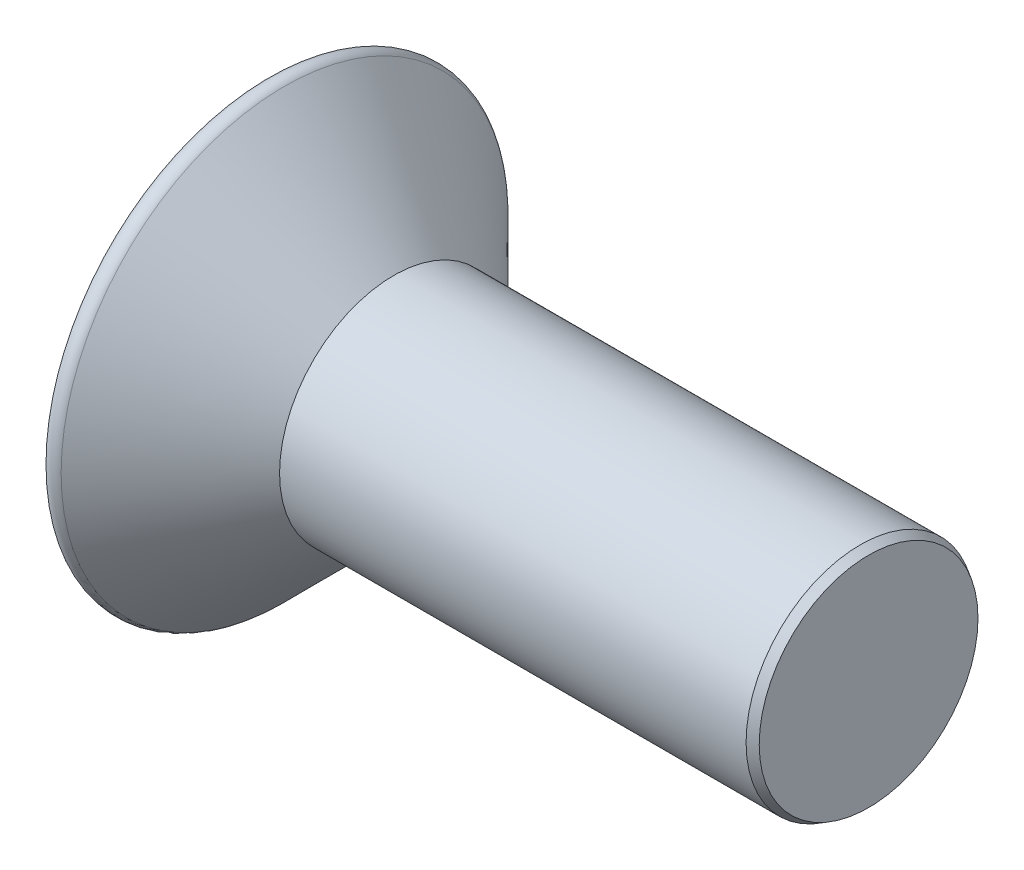
SolidWorks part; units mm, degrees
ref_plane "Front Plane" through (0, 0, 0) normal (0, 0, 1) x (1, 0, 0)
ref_plane "Top Plane" through (0, 0, 0) normal (0, 1, 0) x (1, 0, 0)
ref_plane "Right Plane" through (0, 0, 0) normal (1, 0, 0) x (0, 0, -1)
sketch "Sketch1" plane through (0, 0, 0) normal (0, 0, 1) x (1, 0, 0)
  line L0 (0, 0) -> (6.2784, 0) construction
  line L3 (-7.55, 0) -> (-7.55, -1.8061) construction
  line L4 (-7.55, 0) -> (19.75, 0)
  line L5 (0, 4.75) -> (19.75, 4.75)
  line L6 (19.75, 4.75) -> (19.75, 0)
  line L7 (0, 4.75) -> (-4.5425, 9.2925)
  arc A0 (-5.25, 9.1875) -> (-7.55, 0) centre (11.95, 0) ccw
  arc A1 (-5.25, 9.1875) -> (-4.5425, 9.2925) centre (-4.8573, 8.9777) cw
  dimension "D1" = 45
revolve "Revolve1" add sketch "Sketch1" angle 360 about L0
cosmetic thread "ThreadCosmetic" [suppressed] parameters "D1"=31.8, "D2"=7.85
chamfer "Chamfer1" distance 0.2 angle 60 1 edges at (19.75, 0, 4.75) first distance on face at (19.75, 0, 4.75)
sketch "Sketch5" plane through (0, 0, 0) normal (0, 0, 1) x (1, 0, 0)
  line L0 (1.8337, 3.925) -> (0.6863, 3.925)
  line L1 (0.6863, 3.925) -> (0.21, 4.75)
  line L2 (1.8337, 3.925) -> (2.31, 4.75)
  line L3 (0.21, 4.75) -> (0.21, 5)
  line L4 (2.31, 4.75) -> (2.31, 5)
  line L5 (0.21, 5) -> (2.31, 5)
  line L6 (1.26, 3.925) -> (1.26, 0) construction
  line L7 (0, 0) -> (7.3035, 0) construction
  line L9 (0, 4.75) -> (0, -4.75) construction
  line L12 (19.4036, 4.75) -> (0, 4.75) construction
  dimension "D2" = 60
  dimension "D3" = 0.25
  dimension "minordia" = 7.85
  dimension "threadstart" = 1.26
revolve "ThreadSchematic" [suppressed] cut sketch "Sketch5" angle 360 about L7
pattern_linear "ThdSchPat" [suppressed] count 13 spacing 2.1 along (1, 0, 0) of bodies 105
sketch "Sketch2" plane through (0, 0, 0) normal (0, 0, 1) x (1, 0, 0)
  line L0 (0, 0) -> (5.7679, 0) construction
  line L1 (19.75, 0) -> (11.5228, 4.75)
  line L2 (19.75, 4.75) -> (19.75, 0) construction
  line L4 (11.5228, 4.75) -> (11.5228, 4.85)
  line L5 (11.5228, 4.85) -> (19.85, 4.85)
  line L6 (19.85, 4.85) -> (19.85, 0)
  line L7 (19.85, 0) -> (19.75, 0)
  point P5 (0, 4.75)
  dimension "D1" = 30
  dimension "D2" = 0.1
  dimension "D3" = 0.1
revolve "EndCone" [suppressed] cut sketch "Sketch2" angle 360 about L0
ref_plane "Plane4" through (-7.55, 0, 0) normal (1, 0, 0) x (0, 0, -1)
sketch "Sketch3" plane through (-7.55, 0, 0) normal (1, 0, 0) x (0, 0, -1)
  line L0 (0, 2.343) -> (0, -2.4842) construction
  line L1 (2.7661, 0) -> (-3.4558, 0) construction
  line L2 (-1.04, 5.2) -> (1.04, 5.2)
  line L3 (1.04, 5.2) -> (0.6933, 3.4667)
  line L4 (0, 0) -> (1.9578, 1.9578) construction
  line L5 (0.6933, 3.4667) -> (1.7084, 1.7084)
  line L6 (0.6933, 3.4667) -> (0, 0) construction
  line L7 (-0.6933, 3.4667) -> (-1.7084, 1.7084)
  line L8 (-1.04, 5.2) -> (-0.6933, 3.4667)
  line L9 (5.2, 1.04) -> (5.2, -1.04)
  line L10 (5.2, -1.04) -> (3.4667, -0.6933)
  line L11 (3.4667, -0.6933) -> (1.7084, -1.7084)
  line L12 (3.4667, 0.6933) -> (1.7084, 1.7084)
  line L13 (5.2, 1.04) -> (3.4667, 0.6933)
  line L14 (1.04, -5.2) -> (-1.04, -5.2)
  line L15 (-1.04, -5.2) -> (-0.6933, -3.4667)
  line L16 (-0.6933, -3.4667) -> (-1.7084, -1.7084)
  line L17 (0.6933, -3.4667) -> (1.7084, -1.7084)
  line L18 (1.04, -5.2) -> (0.6933, -3.4667)
  line L19 (-5.2, -1.04) -> (-5.2, 1.04)
  line L20 (-5.2, 1.04) -> (-3.4667, 0.6933)
  line L21 (-3.4667, 0.6933) -> (-1.7084, 1.7084)
  line L22 (-3.4667, -0.6933) -> (-1.7084, -1.7084)
  line L23 (-5.2, -1.04) -> (-3.4667, -0.6933)
  point P14 (0, 5.2)
  point P23 (5.2, 0)
  point P30 (0, -5.2)
  point P37 (-5.2, 0)
  dimension "D1" = 45
  dimension "D3" = 2.08
  dimension "D4" = 75
  dimension "D5" = 6.9333
  dimension "m" = 10.4
extrude "Cut-Extrude1" cut sketch "Sketch3" along normal blind 3.775 draft 6
sketch "Sketch4" plane through (-7.55, 0, 0) normal (1, 0, 0) x (0, 0, -1)
  line L0 (0, 2.1951) -> (0, -2.1951) construction
  line L1 (2.1996, 0) -> (-2.3835, 0) construction
  line L2 (-4.5962, -4.5962) -> (4.5962, 4.5962) construction
  line L3 (5.2, 1.3) -> (-5.2, 1.3)
  line L4 (5.2, 1.3) -> (5.2, -1.3)
  line L5 (5.2, -1.3) -> (-5.2, -1.3)
  line L6 (-5.2, 1.3) -> (-5.2, -1.3)
  line L7 (1.3, 5.2) -> (-1.3, 5.2)
  line L8 (1.3, 5.2) -> (1.3, -5.2)
  line L9 (1.3, -5.2) -> (-1.3, -5.2)
  line L10 (-1.3, 5.2) -> (-1.3, -5.2)
  line L11 (4.5962, 4.5962) -> (2.1123, 1.3)
  line L12 (4.5962, 4.5962) -> (1.3, 2.1123)
  line L13 (1.3, 2.1123) -> (-1.3, 2.1123) construction
  line L14 (0, 0) -> (-4.5962, 4.5962) construction
  line L15 (-4.5962, -4.5962) -> (-1.3, -2.1123)
  line L16 (-4.5962, -4.5962) -> (-2.1123, -1.3)
  line L17 (-1.3, 2.1123) -> (-4.5962, 4.5962)
  line L18 (-4.5962, 4.5962) -> (-2.1123, 1.3)
  line L19 (-2.1123, -1.3) -> (-2.1123, 1.3) construction
  line L20 (2.1123, -1.3) -> (4.5962, -4.5962)
  line L21 (4.5962, -4.5962) -> (1.3, -2.1123)
  circle A0 centre (0, 0) radius 6.5 construction
  dimension "D1" = 13
  dimension "D2" = 2.6
  dimension "m" = 10.4
  dimension "D3" = 45
  dimension "D4" = 8
  dimension "D5" = 45
extrude "TypeZ" [suppressed] cut sketch "Sketch4" along normal blind 3.775
equation "\"D1@ThreadCosmetic\" = \"l@Sketch1\" - \"D1@Chamfer1\""
equation "\"minordia@Sketch5\" = \"D2@ThreadCosmetic\""
equation "\"D1@Plane4\" = \"k@Sketch1\" + \"f@Sketch1\""
equation "\"D5@Sketch3\" = \"m@Sketch3\" * 2 / 3"
equation "\"D3@Sketch3\" = \"m@Sketch3\" / 5"
equation "\"D1@Cut-Extrude1\" =  ( \"k@Sketch1\" + \"f@Sketch1\" )  / 2"
equation "\"D2@Sketch4\" =  \"m@Sketch4\" / 4"
equation "\"D1@TypeZ\" =  ( \"k@Sketch1\" + \"f@Sketch1\" )  / 2"
equation "\"D1@Sketch4\" = \"m@Sketch4\" * 5 / 4"
equation "\"m@Sketch4\" = \"m@Sketch3\""
equation "\"threadstart@Sketch5\" = \"advance@Sketch5\"*0.6"
equation "\"D1@ThdSchPat\" = int(((\"l@Sketch1\"-\"k@Sketch1\")/\"advance@Sketch5\") + 0.999)"
equation "\"D3@ThdSchPat\" = \"advance@Sketch5\""
